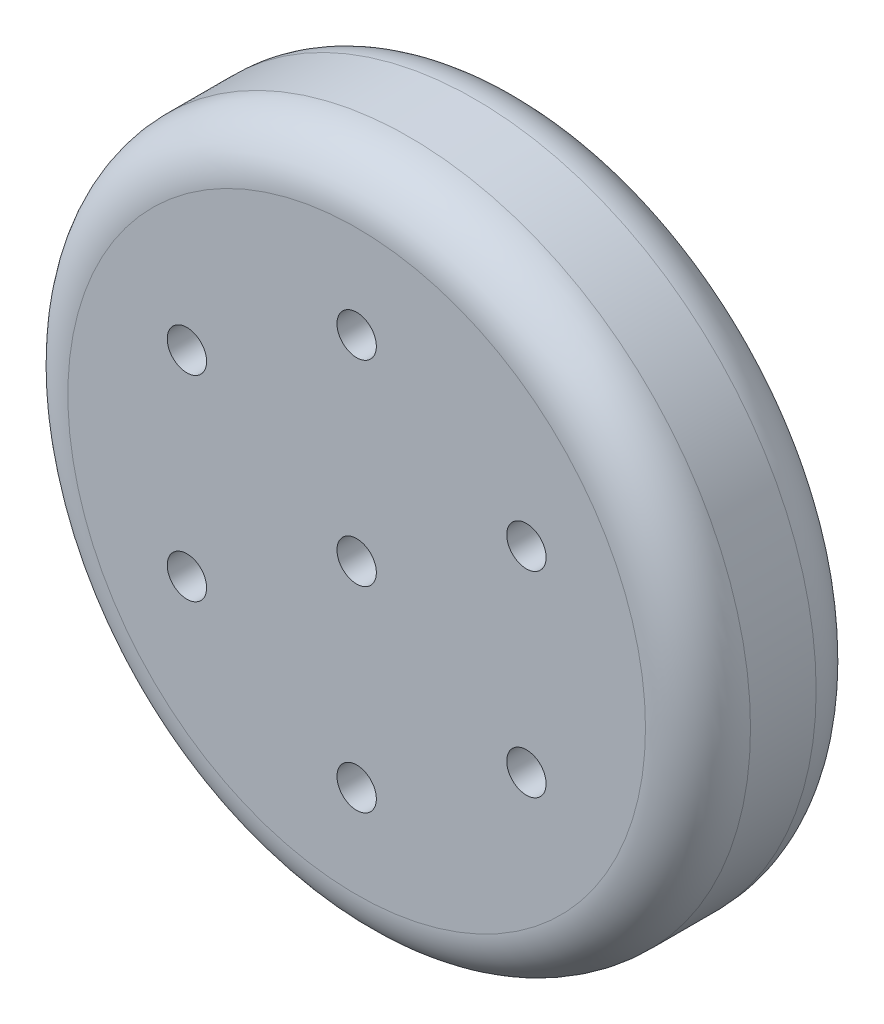
SolidWorks part; units mm, degrees
ref_plane "前视基准面" through (0, 0, 0) normal (0, 0, 1) x (1, 0, 0)
ref_plane "上视基准面" through (0, 0, 0) normal (0, 1, 0) x (1, 0, 0)
ref_plane "右视基准面" through (0, 0, 0) normal (1, 0, 0) x (0, 0, -1)
other "Configuration Table"
sketch "草图1" plane through (0, 0, 0) normal (0, 0, 1) x (1, 0, 0)
  line L0 (0, -21) -> (0, 21) construction
  line L1 (-3, -21) -> (-3, 21)
  line L2 (3, -21) -> (3, 21)
  line L3 (-18.1865, 10.5) -> (18.1865, -10.5) construction
  line L4 (-16.6865, 13.0981) -> (19.6865, -7.9019)
  line L5 (-19.6865, 7.9019) -> (16.6865, -13.0981)
  line L6 (18.1865, 10.5) -> (-18.1865, -10.5) construction
  line L7 (19.6865, 7.9019) -> (-16.6865, -13.0981)
  line L8 (16.6865, 13.0981) -> (-19.6865, -7.9019)
  circle A0 centre (0, 0) radius 12.5
  circle A1 centre (0, 0) radius 17.35
  circle A2 centre (0, 0) radius 26
  circle A3 centre (0, 14.925) radius 1.5
  circle A4 centre (12.9254, -7.4625) radius 1.5
  circle A5 centre (-12.9254, -7.4625) radius 1.5
  circle A6 centre (0, 0) radius 1.5
  arc A7 (-3, -21) -> (3, -21) centre (0, -21) ccw
  arc A8 (3, 21) -> (-3, 21) centre (0, 21) ccw
  arc A9 (-16.6865, 13.0981) -> (-19.6865, 7.9019) centre (-18.1865, 10.5) ccw
  arc A10 (16.6865, -13.0981) -> (19.6865, -7.9019) centre (18.1865, -10.5) ccw
  arc A11 (19.6865, 7.9019) -> (16.6865, 13.0981) centre (18.1865, 10.5) ccw
  arc A12 (-19.6865, -7.9019) -> (-16.6865, -13.0981) centre (-18.1865, -10.5) ccw
  circle A13 centre (12.9254, 7.4625) radius 1.5
  circle A14 centre (12.9254, -7.4625) radius 1.5
  circle A15 centre (0, -14.925) radius 1.5
  circle A16 centre (-12.9254, -7.4625) radius 1.5
  circle A17 centre (-12.9254, 7.4625) radius 1.5
  point P14 (0, 0)
  point P24 (0, 0)
  point P31 (0, 0)
  dimension "D1" = 52
  dimension "D2" = 34.7
  dimension "D3" = 25
  dimension "D4" = 3
  dimension "D7" = 3
  dimension "D5" = 14.925
  dimension "D8" = 6
  dimension "D9" = 42
  dimension "D6" = 3
  dimension "D10" = 3
  dimension "D11" = 6
extrude "凸台-拉伸1" add sketch "草图1" along normal blind 10 contours A2 A12 L8 A1 L5 A9 L4 L1 A8 L2 A11 L7 A10 A7 region at (-25.2646, 0, 0)
sketch "草图2" plane through (0, 0, 10) normal (0, 0, 1) x (1, 0, 0)
  circle A0 centre (0, 0) radius 26
  circle A1 centre (0, 14.93) radius 1.5
  circle A2 centre (12.9298, 7.465) radius 1.5
  circle A3 centre (12.9298, -7.465) radius 1.5
  circle A4 centre (0, -14.93) radius 1.5
  circle A5 centre (-12.9298, -7.465) radius 1.5
  circle A6 centre (-12.9298, 7.465) radius 1.5
  circle A7 centre (0, 0) radius 1.5
  point P4 (0, 0)
  dimension "D2" = 3
  dimension "D4" = 3
  dimension "D1" = 14.93
  dimension "D3" = 6
extrude "凸台-拉伸2" add sketch "草图2" along normal blind 3
fillet "圆角1" radius 4 2 edges at (26, 0, 13) (26, 0, 0)
fillet "圆角2" radius 4 6 edges at (-17.35, 0, 0) (-8.675, 15.0255, 0) (8.675, 15.0255, 0) (17.35, 0, 0) (8.675, -15.0255, 0) (-8.675, -15.0255, 0)
